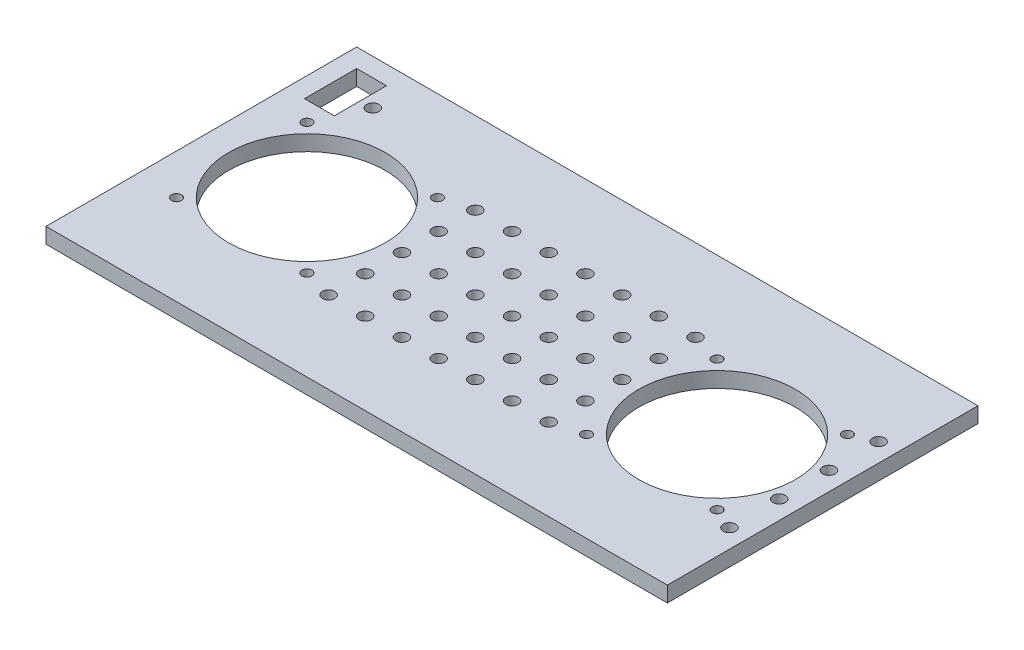
SolidWorks part; units mm, degrees
ref_plane "Front Plane" through (0, 0, 0) normal (0, 0, 1) x (1, 0, 0)
ref_plane "Top Plane" through (0, 0, 0) normal (0, 1, 0) x (1, 0, 0)
ref_plane "Right Plane" through (0, 0, 0) normal (1, 0, 0) x (0, 0, -1)
sketch "Sketch1" plane through (0, 0, 0) normal (0, 1, 0) x (1, 0, 0)
  line L1 (-189.0143, 48.0204) -> (64.9857, 48.0204)
  line L2 (-189.0143, 48.0204) -> (-189.0143, -78.9796)
  line L3 (-189.0143, -78.9796) -> (64.9857, -78.9796)
  line L4 (64.9857, 48.0204) -> (64.9857, -78.9796)
  dimension "D1" = 254
  dimension "D2" = 127
extrude "Boss-Extrude1" add sketch "Sketch1" along normal blind 6.35 contours L1 L4 L3 L2
sketch "Sketch3" plane through (0, 6.35, 0) normal (0, 1, 0) x (1, 0, 0)
  line L0 (-145.8343, 48.0204) -> (-145.8343, -78.9796) construction
  line L1 (-189.0143, 48.0204) -> (64.9857, 48.0204) construction
  line L2 (-189.0143, -78.9796) -> (64.9857, -78.9796) construction
  line L3 (21.8057, 48.0204) -> (21.8057, -78.9796) construction
  line L4 (-189.0143, 48.0204) -> (-189.0143, -78.9796) construction
  line L5 (64.9857, 48.0204) -> (64.9857, -78.9796) construction
  line L6 (-189.0143, -15.4796) -> (64.9857, -15.4796) construction
  line L7 (-181.3943, 19.0644) -> (-169.2023, 19.0644)
  line L8 (-169.2023, 29.7324) -> (-145.8343, 29.7324) construction
  line L9 (-4.8643, -42.1496) -> (48.4757, -42.1496) construction
  line L10 (-172.5043, -42.1496) -> (-119.1643, -42.1496) construction
  line L11 (-172.5043, -42.1496) -> (-172.5043, 11.1904) construction
  line L12 (-181.3943, 19.0644) -> (-181.3943, 40.4004)
  line L13 (-181.3943, 40.4004) -> (-169.2023, 40.4004)
  line L14 (-169.2023, 19.0644) -> (-169.2023, 40.4004)
  line L15 (-172.5043, 11.1904) -> (-119.1643, 11.1904) construction
  line L16 (-119.1643, -42.1496) -> (-119.1643, 11.1904) construction
  line L17 (-172.5043, -42.1496) -> (-119.1643, 11.1904) construction
  line L18 (-172.5043, 11.1904) -> (-119.1643, -42.1496) construction
  line L19 (-4.8643, -42.1496) -> (-4.8643, 11.1904) construction
  line L20 (-4.8643, 11.1904) -> (48.4757, 11.1904) construction
  line L21 (48.4757, -42.1496) -> (48.4757, 11.1904) construction
  line L22 (-4.8643, -42.1496) -> (48.4757, 11.1904) construction
  line L23 (-4.8643, 11.1904) -> (48.4757, -42.1496) construction
  circle A0 centre (-145.8343, -15.4796) radius 32.004
  circle A1 centre (21.8057, -15.4796) radius 32.004
  circle A2 centre (-106.9723, 14.4924) radius 2.54
  circle A3 centre (-172.5043, -42.1496) radius 2.0574
  circle A4 centre (57.3657, 15.0004) radius 2.54
  circle A5 centre (-164.1223, 29.7324) radius 2.54
  circle A6 centre (-119.1643, -42.1496) radius 2.0574
  circle A7 centre (-172.5043, 11.1904) radius 2.0574
  circle A8 centre (-119.1643, 11.1904) radius 2.0574
  circle A9 centre (-4.8643, -42.1496) radius 2.0574
  circle A10 centre (48.4757, -42.1496) radius 2.0574
  circle A11 centre (-4.8643, 11.1904) radius 2.0574
  circle A12 centre (48.4757, 11.1904) radius 2.0574
  point P41 (-145.8343, -15.4796)
  point P50 (21.8057, -15.4796)
  dimension "D4" = 38.862
  dimension "D5" = 64.008
  dimension "D6" = 64.008
  dimension "D9" = 5.08
  dimension "D10" = 7.62
  dimension "D12" = 5.08
  dimension "D13" = 5.08
  dimension "D14" = 5.08
  dimension "D20" = 4.1148
  dimension "D21" = 4.1148
  dimension "D1" = 43.18
  dimension "D2" = 167.64
  dimension "D3" = 43.18
  dimension "D7" = 12.192
  dimension "D8" = 21.336
  dimension "D11" = 7.62
  dimension "D15" = 7.62
  dimension "D16" = 33.02
  dimension "D17" = 33.528
  dimension "D18" = 53.34
  dimension "D19" = 53.34
extrude "Cut-Extrude3" cut sketch "Sketch3" against normal blind 25.4 contours A4
pattern_linear "LPattern1" count 4 spacing 20.32 along (0, 0, 1) of "Cut-Extrude3"
extrude "Cut-Extrude4" cut sketch "Sketch3<7>" against normal blind 25.4 contours A2
sketch "Sketch3<7>" plane through (0, 6.35, 0) normal (0, 1, 0) x (1, 0, 0) same geometry as "Sketch3"
pattern_linear "LPattern2" count 7 spacing 15 along (1, 0, 0) count 5 spacing 15 along (0, 0, 1) of "Cut-Extrude4"
extrude "Cut-Extrude5" cut sketch "Sketch3<8>" against normal blind 25.4
sketch "Sketch3<8>" plane through (0, 6.35, 0) normal (0, 1, 0) x (1, 0, 0) same geometry as "Sketch3"
